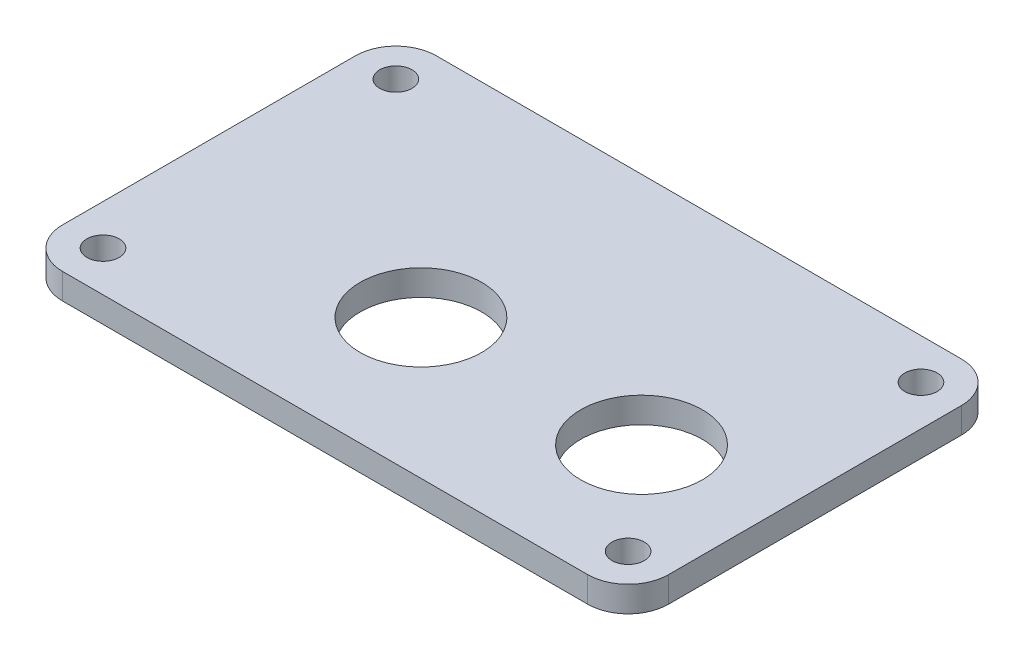
SolidWorks part; units mm, degrees
ref_plane "Front Plane" through (0, 0, 0) normal (0, 0, 1) x (1, 0, 0)
ref_plane "Top Plane" through (0, 0, 0) normal (0, 1, 0) x (1, 0, 0)
ref_plane "Right Plane" through (0, 0, 0) normal (1, 0, 0) x (0, 0, -1)
sketch "Sketch1" plane through (0, 0, 0) normal (0, 1, 0) x (1, 0, 0)
  line L1 (-30, -18.5) -> (30, -18.5)
  line L2 (-30, -18.5) -> (-30, 18.5)
  line L3 (-30, 18.5) -> (30, 18.5)
  line L4 (30, -18.5) -> (30, 18.5)
  line L5 (-30, -18.5) -> (30, 18.5) construction
  line L6 (-30, 18.5) -> (30, -18.5) construction
  point P0 (0, 0)
  dimension "D1" = 37
  dimension "D2" = 60
extrude "Boss-Extrude1" add sketch "Sketch1" along normal blind 2.54
fillet "Fillet1" radius 4 4 edges at (-30, 1.27, -18.5) (30, 1.27, -18.5) (30, 1.27, 18.5) (-30, 1.27, 18.5)
sketch "Sketch2" plane through (0, 2.54, 0) normal (0, 1, 0) x (1, 0, 0)
  circle A0 centre (-26, 14.5) radius 1.6
  circle A1 centre (-26, -14.5) radius 1.6
  circle A2 centre (26, -14.5) radius 1.6
  circle A3 centre (26, 14.5) radius 1.6
  dimension "D1" = 3.2
extrude "Cut-Extrude1" cut sketch "Sketch2" against normal through all
sketch "Sketch3" plane through (0, 2.54, 0) normal (0, 1, 0) x (1, 0, 0)
  line L0 (-4.318, -4.699) -> (17.526, -4.699) construction
  line L1 (0, 0) -> (17.526, 0) construction
  line L2 (17.526, 0) -> (17.526, -4.699) construction
  line L5 (-4.318, 0) -> (-4.318, -4.699) construction
  line L6 (-4.318, 0) -> (0, 0) construction
  circle A0 centre (-4.318, -4.699) radius 6.0198
  circle A1 centre (17.526, -4.699) radius 6.0198
  dimension "D1" = 12.0396
  dimension "D2" = 17.526
  dimension "D3" = 4.699
  dimension "D4" = 4.318
extrude "Cut-Extrude2" cut sketch "Sketch3" against normal through all
